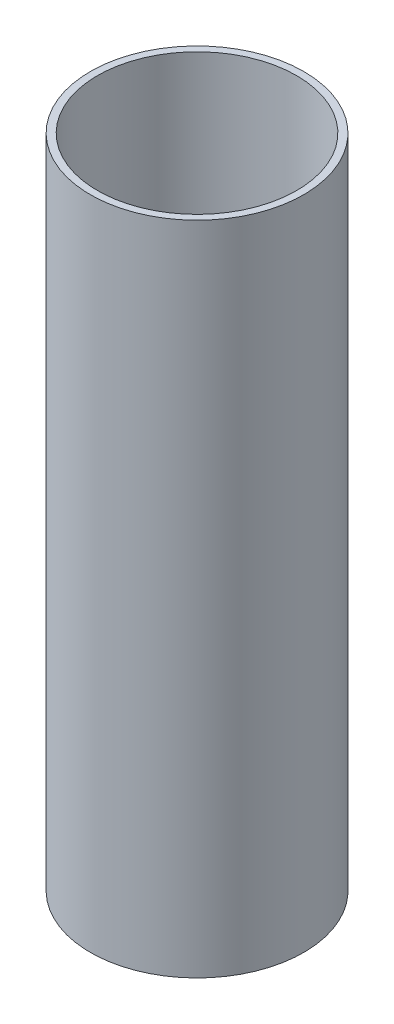
SolidWorks part; units mm, degrees
material "Hexcel AS4C (3000 Filaments)"
ref_plane "Front Plane" through (0, 0, 0) normal (0, 0, 1) x (1, 0, 0)
ref_plane "Top Plane" through (0, 0, 0) normal (0, 1, 0) x (1, 0, 0)
ref_plane "Right Plane" through (0, 0, 0) normal (1, 0, 0) x (0, 0, -1)
sketch "Sketch1" plane through (0, 0, 0) normal (0, 0, 1) x (1, 0, 0)
  line L0 (0, 0) -> (0, 43.8892) construction
  line L1 (26.9875, -18.2798) -> (28.9179, -18.2798)
  line L2 (26.9875, -18.2798) -> (26.9875, -196.0798)
  line L3 (26.9875, -196.0798) -> (28.9179, -196.0798)
  line L4 (28.9179, -18.2798) -> (28.9179, -196.0798)
revolve "Revolve1" add sketch "Sketch1" angle 360 about L0
